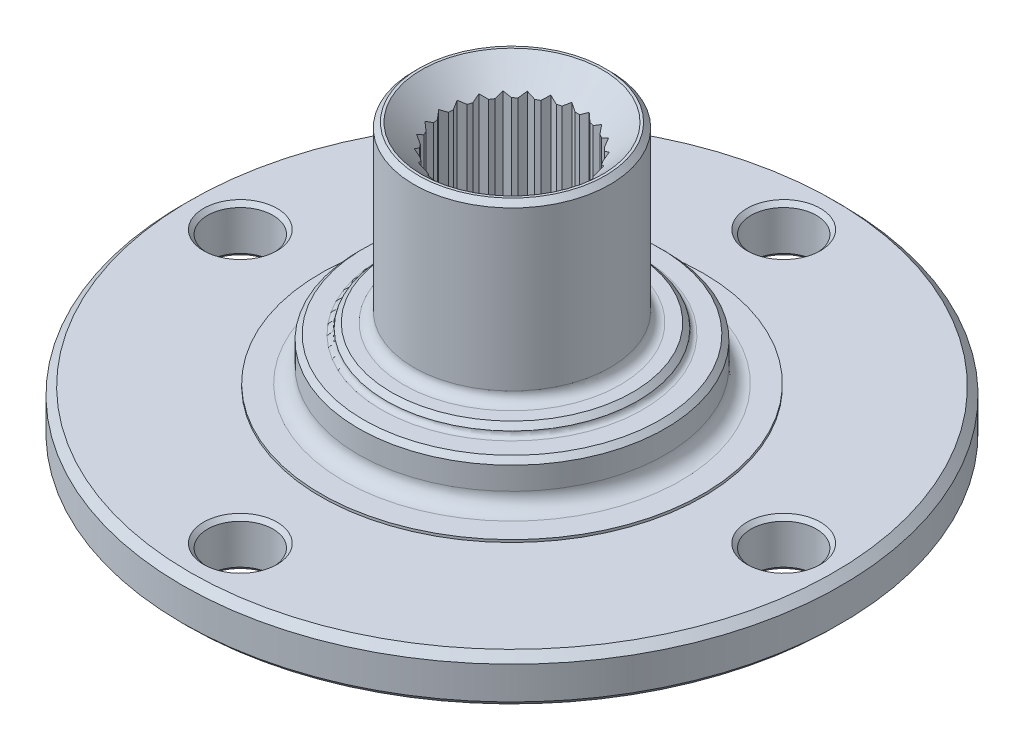
SolidWorks part; units mm, degrees
ref_plane "Plano frontal" through (0, 0, 0) normal (0, 0, 1) x (1, 0, 0)
ref_plane "Plano superior" through (0, 0, 0) normal (0, 1, 0) x (1, 0, 0)
ref_plane "Plano direito" through (0, 0, 0) normal (1, 0, 0) x (0, 0, -1)
sketch "Esboço1" plane through (0, 0, 0) normal (0, 0, 1) x (1, 0, 0)
  line L0 (11.2994, -35.954) -> (11.2994, 37.1181) construction
  line L1 (30.7994, 33.6654) -> (24.2994, 33.6654)
  line L2 (24.2994, 33.6654) -> (24.2994, -22.8346)
  line L3 (24.2994, -22.8346) -> (39.2994, -22.8346)
  line L4 (39.2994, -22.8346) -> (39.2994, -40.8346)
  line L5 (39.2994, -40.8346) -> (42.7994, -40.8346)
  line L6 (42.7994, -40.8346) -> (42.7994, -27.8346)
  line L7 (42.7994, -27.8346) -> (42.9494, -27.8346)
  line L8 (42.9494, -27.8346) -> (42.9494, -21.3346)
  line L9 (42.9494, -21.3346) -> (76.7994, -21.3346)
  line L10 (76.7994, -21.3346) -> (76.7994, -11.8346)
  line L12 (49.2994, -11.8346) -> (49.2994, -11.3346)
  line L13 (49.2994, -11.3346) -> (41.7994, -11.3346)
  line L14 (41.7994, -11.3346) -> (41.7994, -2.8346)
  line L15 (41.7994, -2.8346) -> (36.2994, -2.8346)
  line L16 (36.2994, -2.8346) -> (36.2994, -0.8346)
  line L17 (30.7994, 33.6654) -> (30.7994, -0.8346)
  line L18 (30.7994, -0.8346) -> (36.2994, -0.8346)
  line L19 (49.2994, -11.8346) -> (76.7994, -11.8346)
  dimension "D1" = 13
  dimension "D2" = 19.5
  dimension "D3" = 25
  dimension "D4" = 30.5
  dimension "D5" = 38
  dimension "D6" = 65.5
  dimension "D7" = 31.65
  dimension "D8" = 31.5
  dimension "D9" = 28
  dimension "D10" = 34.5
  dimension "D11" = 36.5
  dimension "D12" = 45
  dimension "D13" = 9.5
  dimension "D14" = 6.5
  dimension "D15" = 19.5
  dimension "D16" = 18
  dimension "D17" = 74.5
revolve "Revolução1" add sketch "Esboço1" angle 360 about L0
chamfer "Chanfro1" distance 5 angle 45 1 edges at (11.2994, 33.6654, -13)
sketch "Esboço2" plane through (0, -22.8346, 0) normal (0, -1, 0) x (1, 0, 0)
  line L0 (11.2994, 0) -> (11.2994, 16.2544) construction
  line L1 (11.2994, 13.7335) -> (9.7994, 12.7335)
  line L2 (9.7994, 12.7335) -> (12.7994, 12.7335)
  line L3 (12.7994, 12.7335) -> (11.2994, 13.7335)
  line L4 (14.7148, 13.302) -> (13.0132, 12.7065)
  line L5 (13.0132, 12.7065) -> (15.9189, 11.9604)
  line L6 (15.9189, 11.9604) -> (14.7148, 13.302)
  line L7 (17.9155, 12.0347) -> (16.1193, 11.8811)
  line L8 (16.1193, 11.8811) -> (18.7482, 10.4358)
  line L9 (18.7482, 10.4358) -> (17.9155, 12.0347)
  line L10 (20.7006, 10.0113) -> (18.9226, 10.3091)
  line L11 (18.9226, 10.3091) -> (21.1095, 8.2555)
  line L12 (21.1095, 8.2555) -> (20.7006, 10.0113)
  line L13 (22.8949, 7.3588) -> (21.2469, 8.0894)
  line L14 (21.2469, 8.0894) -> (22.8544, 5.5565)
  line L15 (22.8544, 5.5565) -> (22.8949, 7.3588)
  line L16 (24.3607, 4.2439) -> (22.9461, 5.3614)
  line L17 (22.9461, 5.3614) -> (23.8732, 2.5083)
  line L18 (23.8732, 2.5083) -> (24.3607, 4.2439)
  line L19 (25.0058, 0.8623) -> (23.9136, 2.2966)
  line L20 (23.9136, 2.2966) -> (24.1019, -0.6975)
  line L21 (24.1019, -0.6975) -> (25.0058, 0.8623)
  line L22 (24.7896, -2.5734) -> (24.0884, -0.9126)
  line L23 (24.0884, -0.9126) -> (23.5262, -3.8594)
  line L24 (23.5262, -3.8594) -> (24.7896, -2.5734)
  line L25 (23.7258, -5.8474) -> (23.4596, -4.0644)
  line L26 (23.4596, -4.0644) -> (22.1823, -6.7789)
  line L27 (22.1823, -6.7789) -> (23.7258, -5.8474)
  line L28 (21.8812, -8.7541) -> (22.0668, -6.9609)
  line L29 (22.0668, -6.9609) -> (20.1546, -9.2724)
  line L30 (20.1546, -9.2724) -> (21.8812, -8.7541)
  line L31 (19.3717, -11.1106) -> (19.9975, -9.4199)
  line L32 (19.9975, -9.4199) -> (17.5704, -11.1833)
  line L33 (17.5704, -11.1833) -> (19.3717, -11.1106)
  line L34 (16.355, -12.7691) -> (17.3815, -11.2871)
  line L35 (17.3815, -11.2871) -> (14.5922, -12.3915)
  line L36 (14.5922, -12.3915) -> (16.355, -12.7691)
  line L37 (13.0206, -13.6252) -> (14.3835, -12.4451)
  line L38 (14.3835, -12.4451) -> (11.4071, -12.8211)
  line L39 (11.4071, -12.8211) -> (13.0206, -13.6252)
  line L40 (9.5781, -13.6252) -> (11.1916, -12.8211)
  line L41 (11.1916, -12.8211) -> (8.2153, -12.4451)
  line L42 (8.2153, -12.4451) -> (9.5781, -13.6252)
  line L43 (6.2437, -12.7691) -> (8.0065, -12.3915)
  line L44 (8.0065, -12.3915) -> (5.2172, -11.2871)
  line L45 (5.2172, -11.2871) -> (6.2437, -12.7691)
  line L46 (3.227, -11.1106) -> (5.0283, -11.1833)
  line L47 (5.0283, -11.1833) -> (2.6013, -9.4199)
  line L48 (2.6013, -9.4199) -> (3.227, -11.1106)
  line L49 (0.7175, -8.7541) -> (2.4442, -9.2724)
  line L50 (2.4442, -9.2724) -> (0.5319, -6.9609)
  line L51 (0.5319, -6.9609) -> (0.7175, -8.7541)
  line L52 (-1.1271, -5.8474) -> (0.4164, -6.7789)
  line L53 (0.4164, -6.7789) -> (-0.8609, -4.0644)
  line L54 (-0.8609, -4.0644) -> (-1.1271, -5.8474)
  line L55 (-2.1909, -2.5734) -> (-0.9275, -3.8594)
  line L56 (-0.9275, -3.8594) -> (-1.4896, -0.9126)
  line L57 (-1.4896, -0.9126) -> (-2.1909, -2.5734)
  line L58 (-2.407, 0.8623) -> (-1.5032, -0.6975)
  line L59 (-1.5032, -0.6975) -> (-1.3148, 2.2966)
  line L60 (-1.3148, 2.2966) -> (-2.407, 0.8623)
  line L61 (-1.762, 4.2439) -> (-1.2744, 2.5083)
  line L62 (-1.2744, 2.5083) -> (-0.3474, 5.3614)
  line L63 (-0.3474, 5.3614) -> (-1.762, 4.2439)
  line L64 (-0.2962, 7.3588) -> (-0.2556, 5.5565)
  line L65 (-0.2556, 5.5565) -> (1.3519, 8.0894)
  line L66 (1.3519, 8.0894) -> (-0.2962, 7.3588)
  line L67 (1.8982, 10.0113) -> (1.4892, 8.2555)
  line L68 (1.4892, 8.2555) -> (3.6762, 10.3091)
  line L69 (3.6762, 10.3091) -> (1.8982, 10.0113)
  line L70 (4.6832, 12.0347) -> (3.8505, 10.4358)
  line L71 (3.8505, 10.4358) -> (6.4794, 11.8811)
  line L72 (6.4794, 11.8811) -> (4.6832, 12.0347)
  line L73 (7.884, 13.302) -> (6.6798, 11.9604)
  line L74 (6.6798, 11.9604) -> (9.5856, 12.7065)
  line L75 (9.5856, 12.7065) -> (7.884, 13.302)
  dimension "D1" = 3
  dimension "D2" = 1.5
  dimension "D3" = 1
  dimension "D4" = 25
extrude "Corte-extrusão1" cut sketch "Esboço2" against normal through all
chamfer "Chanfro2" distance 1 angle 45 3 edges at (11.2994, -0.8346, -25) (11.2994, -2.8346, -30.5) (11.2994, 33.6654, -19.5)
fillet "Filete1" radius 2 1 edges at (11.2994, -0.8346, -19.5)
fillet "Filete2" radius 1 1 edges at (11.2994, -2.8346, -25)
fillet "Filete3" radius 3 1 edges at (11.2994, -11.3346, -30.5)
chamfer "Chanfro3" distance 1.5 angle 45 2 edges at (11.2994, -11.8346, -65.5) (11.2994, -21.3346, -65.5)
fillet "Filete4" radius 2 1 edges at (11.2994, -21.3346, -31.65)
fillet "Filete5" radius 1 1 edges at (11.2994, -22.8346, -28)
chamfer "Chanfro4" distance 1 angle 45 2 edges at (11.2994, -40.8346, -28) (11.2994, -40.8346, -31.5)
chamfer "Chanfro5" distance 0.5 angle 20 25 edges at (11.2994, -21.3346, -64) (20.1985, -22.8346, -9.4766) (17.5622, -22.8346, -11.392) (14.5323, -22.8346, -12.5916) (11.2994, -22.8346, -13) (8.0664, -22.8346, -12.5916) (5.0366, -22.8346, -11.392) (2.4003, -22.8346, -9.4766) (0.3231, -22.8346, -6.9657) (-1.0644, -22.8346, -4.0172) (-1.675, -22.8346, -0.8163) (-1.4704, -22.8346, 2.436) (-0.4634, -22.8346, 5.5351) (1.2827, -22.8346, 8.2865) (6.5138, -22.8346, 12.0871) (9.67, -22.8346, 12.8975) (12.9287, -22.8346, 12.8975) (16.085, -22.8346, 12.0871) (18.9406, -22.8346, 10.5172) (21.316, -22.8346, 8.2865) (23.0621, -22.8346, 5.5351) (24.0691, -22.8346, 2.436) (24.2737, -22.8346, -0.8163) (23.6631, -22.8346, -4.0172) (22.2756, -22.8346, -6.9657) first distance on face at (11.2994, -19.8346, -65.5) first distance on face at (11.2994, -22.8346, -27)
sketch "Esboço3" plane through (0, -21.3346, 0) normal (0, -1, 0) x (1, 0, 0)
  circle A0 centre (11.2994, 0) radius 54 construction
  circle A1 centre (-42.7006, 0) radius 6.5
  circle A2 centre (11.2994, 54) radius 6.5
  circle A3 centre (65.2994, 0) radius 6.5
  circle A4 centre (11.2994, -54) radius 6.5
  dimension "D1" = 108
  dimension "D2" = 13
  dimension "D3" = 4
extrude "Corte-extrusão2" cut sketch "Esboço3" against normal blind 10
chamfer "Chanfro6" distance 0.8 angle 45 8 edges at (11.2994, -11.8346, -47.5) (11.2994, -21.3346, -60.5) (65.2994, -11.8346, 6.5) (65.2994, -21.3346, -6.5) (11.2994, -11.8346, 60.5) (11.2994, -21.3346, 47.5) (-42.7006, -21.3346, -6.5) (-42.7006, -11.8346, 6.5)
